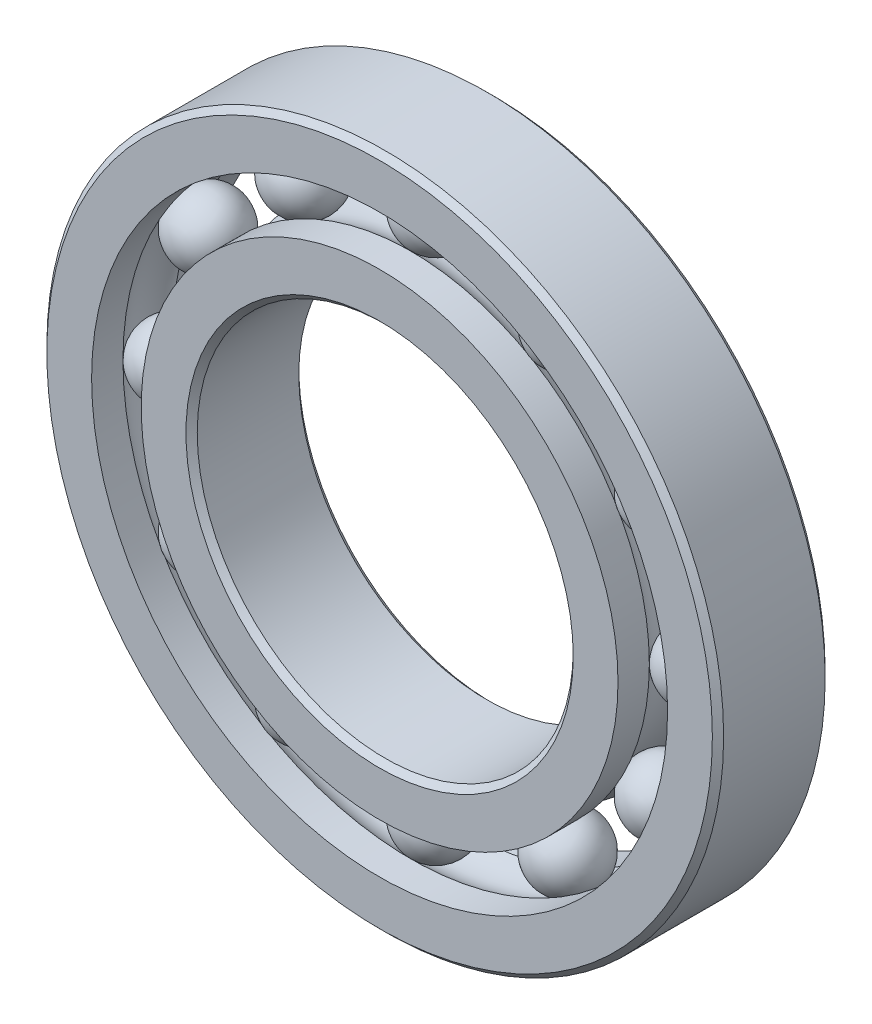
SolidWorks part; units mm, degrees
ref_plane "Front Plane" through (0, 0, 0) normal (0, 0, 1) x (1, 0, 0)
ref_plane "Top Plane" through (0, 0, 0) normal (0, 1, 0) x (1, 0, 0)
ref_plane "Right Plane" through (0, 0, 0) normal (1, 0, 0) x (0, 0, -1)
sketch "Sketch1" plane through (0, 0, 0) normal (1, 0, 0) x (0, 0, -1)
  line L0 (-4.7625, 0) -> (4.7625, 0) construction
  line L1 (0, 28.575) -> (0, -28.575) construction
  line L2 (4.2863, 28.575) -> (-4.2863, 28.575)
  line L3 (-4.2863, 28.575) -> (-4.7625, 28.0988)
  line L4 (-4.7625, 28.0988) -> (-4.7625, 24.3184)
  line L5 (-4.7625, 24.3184) -> (-2.1167, 24.3184)
  line L6 (4.7625, 24.3184) -> (2.1167, 24.3184)
  line L7 (4.7625, 28.0988) -> (4.7625, 24.3184)
  line L8 (4.2863, 28.575) -> (4.7625, 28.0988)
  line L9 (0, 28.575) -> (0, 22.225) construction
  line L10 (0, 22.225) -> (0, 15.875) construction
  arc A0 (-2.1167, 24.3184) -> (2.1167, 24.3184) centre (0, 22.225) cw
  point P14 (0, 15.875)
  dimension "D3" = 4.2333
  dimension "D1" = 45
  dimension "Width" = 9.525
  dimension "OD" = 57.15
  dimension "D2" = 0.4763
  dimension "Shaft Dia" = 31.75
  dimension "D4" = 2.0934
revolve "Revolve1" add sketch "Sketch1" angle 360 about L0
sketch "Sketch3" plane through (0, 0, 0) normal (1, 0, 0) x (0, 0, -1)
  line L0 (-4.7625, 20.1316) -> (-2.1167, 20.1316)
  line L1 (0, 28.575) -> (0, -28.575) construction
  line L2 (-4.7625, 28.0988) -> (-4.7625, 24.3184) construction
  line L3 (-4.7625, 20.1316) -> (-4.7625, 16.3512)
  line L4 (-4.2863, 28.575) -> (-4.7625, 28.0988) construction
  line L5 (-4.7625, 16.3512) -> (-4.2863, 15.875)
  line L6 (-4.2863, 15.875) -> (4.2863, 15.875)
  line L7 (4.2863, 28.575) -> (4.2863, -28.575) construction
  line L8 (4.2863, 15.875) -> (4.7625, 16.3512)
  line L9 (4.7625, -28.0988) -> (4.7625, 28.0988) construction
  line L10 (4.7625, 16.3512) -> (4.7625, 20.1316)
  line L11 (4.7625, 20.1316) -> (2.1167, 20.1316)
  line L13 (4.2863, 28.575) -> (4.7625, 28.0988) construction
  arc A0 (2.1167, 24.3184) -> (-2.1167, 24.3184) centre (0, 22.225) ccw construction
  arc A1 (2.1167, 20.1316) -> (-2.1167, 20.1316) centre (0, 22.225) cw
revolve "Revolve3" add sketch "Sketch3" angle 360 about L0
sketch "Sketch4" plane through (0, 0, 0) normal (1, 0, 0) x (0, 0, -1)
  line L0 (-2.977, 22.225) -> (2.977, 22.225)
  arc A2 (-2.977, 22.225) -> (2.977, 22.225) centre (0, 22.225) cw
  arc A3 (2.1167, 24.3184) -> (-2.1167, 24.3184) centre (0, 22.225) ccw construction
revolve "Revolve4" add sketch "Sketch4" angle 360 about L0
ref_axis "Axis1" through (0, 0, -4.7625) along (0, 0, 1)
pattern_circular "CirPattern1" count 12 every 30 about axis through (0, 0, -4.7625) along (0, 0, 1) of bodies 104
sketch "Sketch5" plane through (0, 0, 0) normal (1, 0, 0) x (0, 0, -1)
  line L0 (-4.7625, 24.3184) -> (-2.1167, 24.3184) construction
  line L1 (-4.5244, 24.3184) -> (-2.977, 24.3184)
  line L2 (-4.5244, 24.3184) -> (-4.5244, 20.1316)
  line L3 (-4.5244, 20.1316) -> (-2.977, 20.1316)
  line L4 (-2.977, 24.3184) -> (-2.977, 20.1316)
  line L5 (-4.7625, 20.1316) -> (-2.1167, 20.1316) construction
  line L6 (4.7625, 24.3184) -> (2.1167, 24.3184) construction
  line L7 (4.5244, 24.3184) -> (2.977, 24.3184)
  line L8 (4.5244, 24.3184) -> (4.5244, 20.1316)
  line L9 (4.5244, 20.1316) -> (2.977, 20.1316)
  line L10 (2.977, 24.3184) -> (2.977, 20.1316)
  line L11 (4.7625, 20.1316) -> (2.1167, 20.1316) construction
  line L12 (-4.2863, 28.575) -> (-4.7625, 28.0988) construction
  point P18 (-4.5244, 28.3369)
revolve "Revolve5" [suppressed] add sketch "Sketch5" angle 360 about L0
equation "\"D2@Sketch1\" = \"Width@Sketch1\"*.05"
equation "\"D3@Sketch1\" = \"Width@Sketch1\"/2.25"
equation "\"D4@Sketch1\" = (((\"OD@Sketch1\"-\"Width@Sketch1\")/2)/3.25)/3.5"
equation "\"D2@CirPattern1\" = 360/\"Balls@CirPattern1\""
